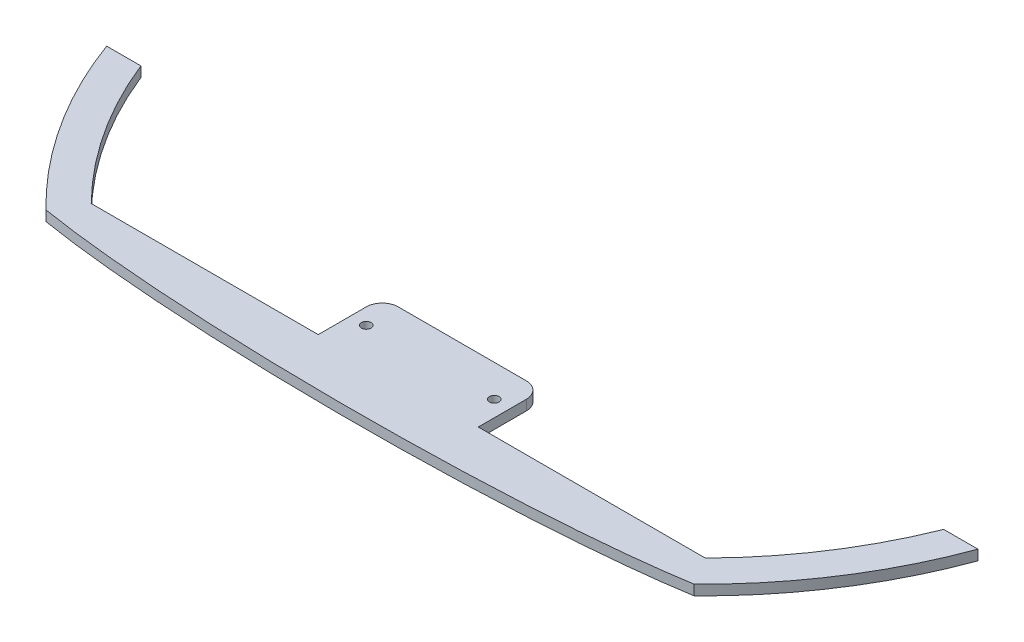
SolidWorks part; units mm, degrees
ref_plane "前视基准面" through (0, 0, 0) normal (0, 0, 1) x (1, 0, 0)
ref_plane "上视基准面" through (0, 0, 0) normal (0, 1, 0) x (1, 0, 0)
ref_plane "右视基准面" through (0, 0, 0) normal (1, 0, 0) x (0, 0, -1)
other "Configuration Table"
sketch "草图1" plane through (0, 0, 0) normal (0, 1, 0) x (1, 0, 0)
  line L0 (0, 0) -> (34.1522, 0) construction
  line L5 (-25, -10) -> (-95.9166, -10)
  line L6 (-20, 10) -> (20, 10)
  line L7 (0, 0) -> (0, 15.8828) construction
  line L8 (-25, 5) -> (-25, -10)
  line L10 (25, 5) -> (25, -10)
  line L11 (25, -10) -> (95.9166, -10)
  line L12 (-136.1066, 35) -> (-125.3994, 35)
  line L13 (125.3994, 35) -> (136.1066, 35)
  circle A0 centre (-20, 0) radius 1.5
  circle A1 centre (20, 0) radius 1.5
  arc A2 (20, 10) -> (25, 5) centre (20, 5) cw
  arc A3 (-20, 10) -> (-25, 5) centre (-20, 5) ccw
  arc A5 (101.2484, -18.7967) -> (136.1066, 35) centre (0, 85) ccw
  arc A6 (95.9166, -10) -> (125.3994, 35) centre (0, 85) ccw
  arc A7 (-136.1066, 35) -> (-101.2484, -18.7967) centre (0, 85) ccw
  arc A8 (-125.3994, 35) -> (-95.9166, -10) centre (0, 85) ccw
  ellipse E0 centre (0, -10) end of major axis (-125, -10) minor radius 15 (-101.2484, -18.7967) -> (101.2484, -18.7967) ccw
  point P0 (0, 0)
  point P24 (25, 10)
  point P30 (0, 85)
  dimension "D1" = 3
  dimension "D3" = 5
  dimension "D10" = 290
  dimension "D11" = 270
  dimension "D2" = 40
  dimension "D4" = 25
  dimension "D5" = 10
  dimension "D6" = 20
  dimension "D9" = 25
  dimension "D12" = 45
extrude "凸台-拉伸1" add sketch "草图1" along normal blind 3.175
